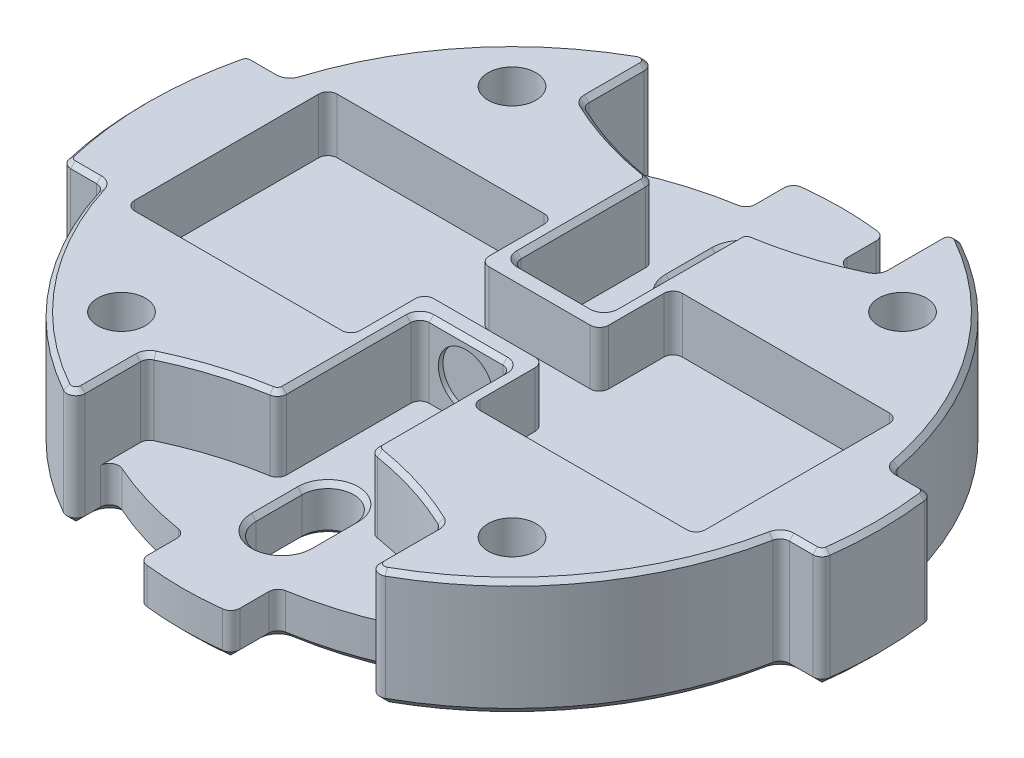
SolidWorks part; units mm, degrees
ref_plane "前视基准面" through (0, 0, 0) normal (0, 0, 1) x (1, 0, 0)
ref_plane "上视基准面" through (0, 0, 0) normal (0, 1, 0) x (1, 0, 0)
ref_plane "右视基准面" through (0, 0, 0) normal (1, 0, 0) x (0, 0, -1)
sketch "草图1" plane through (0, 0, 0) normal (0, 1, 0) x (1, 0, 0)
  line L0 (-40, 0) -> (40, 0) construction
  line L1 (-38.7298, 10) -> (-34.375, 10)
  line L2 (-38.7298, -10) -> (-34.375, -10)
  line L3 (35.2936, 6) -> (39.5474, 6)
  line L4 (35.2936, -6) -> (39.5474, -6)
  arc A0 (-38.7298, 10) -> (-38.7298, -10) centre (0, 0) ccw
  arc A2 (-34.375, -10) -> (35.2936, -6) centre (0, 0) ccw
  arc A3 (39.5474, -6) -> (39.5474, 6) centre (0, 0) ccw
  arc A4 (35.2936, 6) -> (-34.375, 10) centre (0, 0) ccw
  dimension "D1" = 80
  dimension "D2" = 71.6
  dimension "D3" = 12
  dimension "D4" = 20
extrude "凸台-拉伸1" add sketch "草图1" along normal blind 13
sketch "草图2" plane through (0, 13, 0) normal (0, 1, 0) x (1, 0, 0)
  line L0 (-40, 0) -> (40, 0) construction
  line L1 (-5, -5) -> (5, -5)
  line L2 (0, 5) -> (0, -5) construction
  line L3 (-5, -5) -> (-5, -20.3489)
  line L4 (5, -5) -> (5, -20.3489)
  line L5 (0, 5) -> (0, 35.8) construction
  line L6 (16, 23.751) -> (16, 32.0256)
  line L7 (-16, -23.751) -> (-16, -32.0256)
  line L8 (16, -23.751) -> (16, -32.0256)
  line L9 (0, -5) -> (0, -35.8) construction
  line L10 (-16, 23.751) -> (-16, 32.0256)
  line L11 (5, 5) -> (5, 20.3489)
  line L12 (-5, 5) -> (-5, 20.3489)
  line L13 (-5, 5) -> (5, 5)
  arc A0 (16, -23.751) -> (5, -20.3489) centre (0, -56) ccw
  arc A1 (-34.375, -10) -> (35.2936, -6) centre (0, 0) ccw construction
  arc A2 (-16, -32.0256) -> (16, -32.0256) centre (0, 0) ccw
  arc A3 (-5, -20.3489) -> (-16, -23.751) centre (0, -56) ccw
  arc A4 (-38.7298, 10) -> (-38.7298, -10) centre (0, 0) ccw construction
  arc A5 (39.5474, -6) -> (39.5474, 6) centre (0, 0) ccw construction
  arc A6 (-5, 20.3489) -> (-16, 23.751) centre (0, 56) cw
  arc A7 (-16, 32.0256) -> (16, 32.0256) centre (0, 0) cw
  arc A8 (16, 23.751) -> (5, 20.3489) centre (0, 56) cw
  arc M12 (-34.375, -10) -> (35.2936, -6) centre (0, 0) ccw
  dimension "D3" = 72
  dimension "D5" = 51
  dimension "D1" = 5
  dimension "D2" = 10
  dimension "D4" = 32
extrude "切除-拉伸1" cut sketch "草图2" against normal blind 8.1 contours L3 A3 L7 L8 A0 L4 L1 M12 | A6 L10 A7 L6 A8 L11 L13 L12 region at (0, 13, 23.8873)
sketch "草图3" plane through (0, 4.9, 0) normal (0, 1, 0) x (1, 0, 0)
  line L0 (0, -5) -> (0, 5) construction
  line L1 (-5, 30.5501) -> (-5, 35.4491)
  line L2 (5, 30.5501) -> (5, 35.4491)
  line L3 (-5, -30.5501) -> (-5, -35.4491)
  line L4 (5, -30.5501) -> (5, -35.4491)
  line L5 (5, 5) -> (5, 20.3489) construction
  line L6 (-5, 5) -> (-5, 20.3489) construction
  line L7 (5, -5) -> (5, -20.3489) construction
  line L8 (-5, -5) -> (-5, -20.3489) construction
  line L9 (-16, 32.0256) -> (-16, 27.1374)
  line L10 (-16, 23.751) -> (-16, 32.0256) construction
  line L11 (16, 32.0256) -> (16, 27.1374)
  line L12 (-16, -32.0256) -> (-16, -27.1374)
  line L13 (-16, -23.751) -> (-16, -32.0256) construction
  line L14 (16, -32.0256) -> (16, -27.1374)
  arc A0 (16, 27.1374) -> (5, 30.5501) centre (0, -5) ccw
  arc A1 (-16, -27.1374) -> (-5, -30.5501) centre (0, 5) ccw
  arc A2 (16, 32.0256) -> (-16, 32.0256) centre (0, 0) ccw construction
  arc A3 (-16, -32.0256) -> (16, -32.0256) centre (0, 0) ccw construction
  arc A4 (-16, -32.0256) -> (-5, -35.4491) centre (0, 0) ccw
  arc A5 (16, 32.0256) -> (5, 35.4491) centre (0, 0) ccw
  arc A6 (-5, 30.5501) -> (-16, 27.1374) centre (0, -5) ccw
  arc A7 (-5, 35.4491) -> (-16, 32.0256) centre (0, 0) ccw
  arc A8 (5, -30.5501) -> (16, -27.1374) centre (0, 5) ccw
  arc A9 (5, -35.4491) -> (16, -32.0256) centre (0, 0) ccw
  dimension "D1" = 71.8
  dimension "D2" = 10
extrude "切除-拉伸2" cut sketch "草图3" against normal blind 8
sketch "草图7" plane through (0, 13, 0) normal (0, 1, 0) x (1, 0, 0)
  line L0 (-40, 0) -> (40, 0) construction
  line L1 (0, -5) -> (0, 5) construction
  line L2 (-31, 11) -> (-6.5, 11)
  line L3 (-31, 11) -> (-31, -11)
  line L4 (-31, -11) -> (-6.5, -11)
  line L5 (-6.5, 11) -> (-6.5, 3)
  line L6 (6.5, 11) -> (31, 11)
  line L7 (6.5, 11) -> (6.5, 3)
  line L8 (6.5, -11) -> (31, -11)
  line L9 (31, 11) -> (31, -11)
  line L10 (-5, -5) -> (5, -5) construction
  line L11 (-5, 5) -> (5, 5) construction
  line L12 (-6.5, 3) -> (6.5, 3)
  line L13 (-6.5, -3) -> (6.5, -3)
  line L14 (-6.5, -3) -> (-6.5, -11)
  line L15 (6.5, -3) -> (6.5, -11)
  arc A0 (-38.7298, 10) -> (-38.7298, -10) centre (0, 0) ccw construction
  arc A1 (39.5474, -6) -> (39.5474, 6) centre (0, 0) ccw construction
  dimension "D1" = 13
  dimension "D2" = 24.5
  dimension "D3" = 22
  dimension "D4" = 6
extrude "切除-拉伸6" cut sketch "草图7" against normal blind 6
fillet "圆角1" radius 1 48 edges at (16, 2.45, -27.1374) (5, 2.45, -30.5501) (16, 6.5, -32.0256) (35.2936, 6.5, -6) (39.5474, 6.5, -6) (35.2936, 6.5, 6) (39.5474, 6.5, 6) (16, 6.5, 32.0256) (16, 2.45, 27.1374) (5, 2.45, 30.5501) (5, 2.45, 35.4491) (-5, 2.45, 35.4491) (-5, 2.45, 30.5501) (-16, 2.45, 27.1374) (-16, 6.5, 32.0256) (-34.375, 6.5, 10) (-38.7298, 6.5, 10) (-38.7298, 6.5, -10) (-34.375, 6.5, -10) (-16, 6.5, -32.0256) (-16, 2.45, -27.1374) (-5, 2.45, -30.5501) (-5, 2.45, -35.4491) (5, 2.45, -35.4491) (-16, 8.95, -23.751) (16, 8.95, -23.751) (5, 8.95, -20.3489) (-5, 8.95, -20.3489) (-5, 8.95, -5) (5, 8.95, -5) (-6.5, 10, 11) (-31, 10, 11) (-31, 10, -11) (-6.5, 10, -11) (31, 10, -11) (31, 10, 11) (6.5, 10, 11) (6.5, 10, 3) (-6.5, 10, 3) (6.5, 10, -11) (6.5, 10, -3) (-6.5, 10, -3) (-5, 8.95, 5) (5, 8.95, 5) (16, 8.95, 23.751) (5, 8.95, 20.3489) (-5, 8.95, 20.3489) (-16, 8.95, 23.751)
sketch "草图8" plane through (0, 4.9, 0) normal (0, 1, 0) x (1, 0, 0)
  line L0 (0, 35.8) -> (0, -35.8) construction
  line L1 (-31, 0) -> (31, 0) construction
  line L2 (-31, 10) -> (-31, -10) construction
  line L3 (31, -10) -> (31, 10) construction
  line L4 (0, -20) -> (0, -25) construction
  line L5 (2.8, -20) -> (2.8, -25)
  line L6 (-2.8, -20) -> (-2.8, -25)
  line L7 (0, 20) -> (0, 25) construction
  line L8 (2.8, 20) -> (2.8, 25)
  line L9 (-2.8, 20) -> (-2.8, 25)
  arc A0 (4.1149, 35.5627) -> (-4.1149, 35.5627) centre (0, 0) ccw construction
  arc A1 (-4.1149, -35.5627) -> (4.1149, -35.5627) centre (0, 0) ccw construction
  arc A2 (2.8, -20) -> (-2.8, -20) centre (0, -20) ccw
  arc A3 (-2.8, -25) -> (2.8, -25) centre (0, -25) ccw
  arc A4 (2.8, 20) -> (-2.8, 20) centre (0, 20) cw
  arc A5 (-2.8, 25) -> (2.8, 25) centre (0, 25) cw
  point P13 (0, -22.5)
  point P25 (0, 22.5)
  dimension "D1" = 2.8
  dimension "D2" = 5
  dimension "D3" = 40
extrude "切除-拉伸7" cut sketch "草图8" against normal blind 6
chamfer "倒角2" distance 0.5 angle 45 16 edges at (2.8, 0, 22.5) (0, 0, 17.2) (0, 0, 27.8) (-2.8, 0, 22.5) (2.8, 4.9, 22.5) (0, 4.9, 17.2) (0, 4.9, 27.8) (-2.8, 4.9, 22.5) (0, 0, -27.8) (-2.8, 0, -22.5) (2.8, 0, -22.5) (0, 0, -17.2) (0, 4.9, -27.8) (-2.8, 4.9, -22.5) (2.8, 4.9, -22.5) (0, 4.9, -17.2)
chamfer "倒角4" distance 1 angle 45 48 edges at (-27.7923, 0, -22.566) (-34.5254, 0, -10.1941) (-16.4943, 0, -31.2278) (-36.5324, 0, -10) (-16, 0, -29.5394) (-38.5675, 0, -9.7845) (-15.5447, 0, -27.875) (-40, 0, 0) (-10.2992, 0, -29.3909) (-38.5675, 0, 9.7845) (-5.2376, 0, -30.7619) (-36.5324, 0, 10) (-5, 0, -32.9891) (-34.5254, 0, 10.1941) (-4.7466, 0, -35.2346) (-27.7923, 0, 22.566) (0, 0, -35.8) (-16.4943, 0, 31.2278) (4.7466, 0, -35.2346) (-16, 0, 29.5394) (5, 0, -32.9891) (-15.5447, 0, 27.875) (5.2376, 0, -30.7619) (-10.2992, 0, 29.3909) (10.2992, 0, -29.3909) (-5.2376, 0, 30.7619) (15.5447, 0, -27.875) (-5, 0, 32.9891) (16, 0, -29.5394) (-4.7466, 0, 35.2346) (16.4943, 0, -31.2278) (0, 0, 35.8) (29.0136, 0, -20.9727) (4.7466, 0, 35.2346) (35.4918, 0, -6.2286) (5, 0, 32.9891) (37.4031, 0, -6) (5.2376, 0, 30.7619) (39.3384, 0, -5.7511) (10.2992, 0, 29.3909) (40, 0, 0) (15.5447, 0, 27.875) (39.3384, 0, 5.7511) (16, 0, 29.5394) (37.4031, 0, 6) (16.4943, 0, 31.2278) (35.4918, 0, 6.2286) (29.0136, 0, 20.9727)
sketch "草图9" plane through (0, 0, -5) normal (0, 0, -1) x (-1, 0, 0)
  line L0 (0, 13) -> (0, 4.9) construction
  line L1 (4, 13) -> (-4, 13) construction
  line L2 (4, 4.9) -> (-4, 4.9) construction
  circle A0 centre (0, 8.95) radius 3
  dimension "D1" = 6
extrude "切除-拉伸8" cut sketch "草图9" against normal blind 0.5
sketch "草图10" plane through (0, 0, 5) normal (0, 0, 1) x (1, 0, 0)
  line L0 (0, 4.9) -> (0, 13) construction
  line L1 (-4, 4.9) -> (4, 4.9) construction
  line L2 (-4, 13) -> (4, 13) construction
  circle A0 centre (0, 8.95) radius 3
  dimension "D1" = 6
extrude "切除-拉伸9" cut sketch "草图10" against normal blind 0.5
sketch "草图11" plane through (0, 0, 0) normal (0, -1, 0) x (1, 0, 0)
  line L1 (-21.2132, 21.2132) -> (21.2132, 21.2132)
  line L2 (-21.2132, 21.2132) -> (-21.2132, -21.2132)
  line L3 (-21.2132, -21.2132) -> (21.2132, -21.2132)
  line L4 (21.2132, 21.2132) -> (21.2132, -21.2132)
  line L5 (-21.2132, 21.2132) -> (21.2132, -21.2132) construction
  line L6 (-21.2132, -21.2132) -> (21.2132, 21.2132) construction
  circle A0 centre (0, 0) radius 30
  circle A1 centre (-21.2132, 21.2132) radius 2.6
  circle A2 centre (21.2132, 21.2132) radius 2.6
  circle A3 centre (21.2132, -21.2132) radius 2.6
  circle A4 centre (-21.2132, -21.2132) radius 2.6
  point P0 (0, 0)
  point P9 (0, 0)
  point P18 (0, 0)
  dimension "D1" = 60
  dimension "D2" = 5.2
  dimension "D3" = 4
extrude "切除-拉伸10" cut sketch "草图11" against normal blind 15 contours A0 A1 | L1 A1 A0 | A0 A1 L2 | L2 A1 L1 | L1 A2 L4 | L4 A2 A0 | A0 A2 L1 | A0 A2 | L4 A3 L3 | A0 A3 L4 | A0 A3 | L3 A3 A0 | L3 A4 L2 | L2 A4 A0 | A0 A4 | A0 A4 L3 region at (-19.6466, 0, 21.8326) region at (-20.1097, 0, 20.1097) region at (-21.979, 0, 21.979) region at (-21.8326, 0, 19.6466) region at (19.6466, 0, 21.8326) region at (20.1097, 0, 20.1097) region at (-20.1097, 0, -20.1097) region at (-21.8326, 0, -19.6466) region at (21.979, 0, 21.979) region at (-21.979, 0, -21.979) region at (21.8326, 0, 19.6466) region at (-19.6466, 0, -21.8326) region at (21.8326, 0, -19.6466) region at (20.1097, 0, -20.1097) region at (19.6466, 0, -21.8326) region at (21.979, 0, -21.979)
sketch "草图12" plane through (0, 0, 0) normal (0, -1, 0) x (1, 0, 0)
  circle A0 centre (-21.2132, 21.2132) radius 4.5
  circle A1 centre (21.2132, 21.2132) radius 4.5
  circle A2 centre (21.2132, -21.2132) radius 4.5
  circle A3 centre (-21.2132, -21.2132) radius 4.5
  point P3 (0, 0)
  point P12 (0, 0)
  dimension "D1" = 9
  dimension "D2" = 4
extrude "切除-拉伸11" cut sketch "草图12" against normal blind 5.2
chamfer "倒角5" distance 0.5 angle 45 52 edges at (-27.7923, 13, -22.566) (-34.5254, 13, -10.1941) (-16.4943, 13, -31.2278) (-36.5324, 13, -10) (-16, 13, -27.3712) (-38.5675, 13, -9.7845) (-15.8452, 13, -23.8427) (-40, 13, 0) (-10.7383, 13, -21.6388) (-38.5675, 13, 9.7845) (-5.2377, 13, -20.137) (-36.5324, 13, 10) (-5, 13, -12.7449) (-34.5254, 13, 10.1941) (-4.7071, 13, -5.2929) (-27.7923, 13, 22.566) (0, 13, -5) (-16.4943, 13, 31.2278) (4.7071, 13, -5.2929) (-16, 13, 27.3712) (5, 13, -12.7449) (-15.8452, 13, 23.8427) (5.2377, 13, -20.137) (-10.7383, 13, 21.6388) (10.7383, 13, -21.6388) (-5.2377, 13, 20.137) (15.8452, 13, -23.8427) (-5, 13, 12.7449) (16, 13, -27.3712) (-4.7071, 13, 5.2929) (16.4943, 13, -31.2278) (0, 13, 5) (29.0136, 13, -20.9727) (4.7071, 13, 5.2929) (35.4918, 13, -6.2286) (5, 13, 12.7449) (37.4031, 13, -6) (5.2377, 13, 20.137) (39.3384, 13, -5.7511) (10.7383, 13, 21.6388) (40, 13, 0) (15.8452, 13, 23.8427) (39.3384, 13, 5.7511) (16, 13, 27.3712) (37.4031, 13, 6) (16.4943, 13, 31.2278) (35.4918, 13, 6.2286) (29.0136, 13, 20.9727) (-21.2132, 0, -25.7132) (21.2132, 0, -25.7132) (-21.2132, 0, 16.7132) (21.2132, 0, 16.7132)
